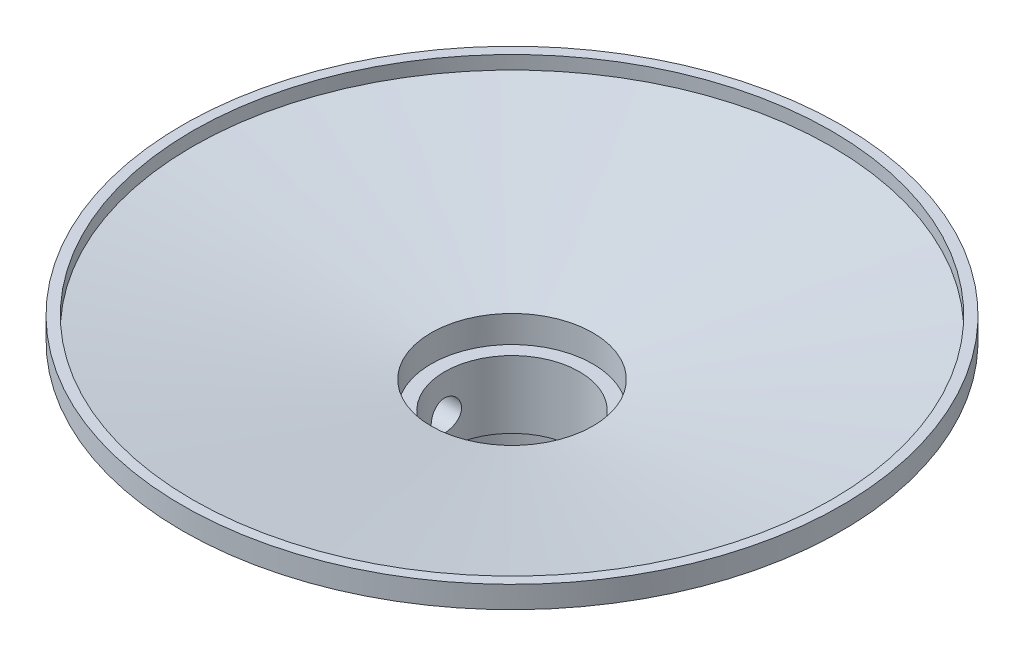
SolidWorks part; units mm, degrees
ref_plane "Front Plane" through (0, 0, 0) normal (0, 0, 1) x (1, 0, 0)
ref_plane "Top Plane" through (0, 0, 0) normal (0, 1, 0) x (1, 0, 0)
ref_plane "Right Plane" through (0, 0, 0) normal (1, 0, 0) x (0, 0, -1)
sketch "Sketch5" plane through (0, 0, 0) normal (1, 0, 0) x (0, 0, -1)
  line L0 (0, 0) -> (0, 10.2777) construction
  line L1 (0, 0) -> (48.9, 0) construction
  line L2 (48.9, 0) -> (48.9, -3.2586)
  line L3 (48.9, -3.2586) -> (13.5, -9.5006)
  line L4 (13.5, -9.5006) -> (13.5, -22.242)
  line L5 (10, -22.242) -> (12, -22.242)
  line L6 (47.4, 0) -> (47.4, -2)
  line L7 (47.4, -2) -> (12, -8.242)
  line L8 (12, -8.242) -> (12, -12.242)
  line L9 (12, -22.242) -> (12, -26.242)
  line L10 (12, -12.242) -> (10, -12.242)
  line L11 (10, -12.242) -> (10, -22.242)
  line L12 (12, -8.242) -> (12, -21.6264) construction
  line L13 (12, -21.6264) -> (0.1924, -33.5895) construction
  line L14 (13.5, -22.242) -> (1.26, -34.6432) construction
  line L15 (12, -26.242) -> (13.5, -26.242)
  line L16 (13.5, -26.242) -> (13.5, -22.242)
  line L17 (47.4, -2) -> (0, -2) construction
  line L18 (47.4, 0) -> (48.9, 0)
  dimension "D1" = 48.9
  dimension "D3" = 10
  dimension "D4" = 2
  dimension "D5" = 4
  dimension "D6" = 10
  dimension "D7" = 2
  dimension "D8" = 10
  dimension "D2" = 1.5
revolve "Revolve5" add sketch "Sketch5" angle 360 about L0 region at (0, -1.6293, -48.4308)
sketch "Sketch6" plane through (0, 0, 0) normal (1, 0, 0) x (0, 0, -1)
  line L0 (-13.5, -9.5006) -> (-13.5, -26.242) construction
  line L1 (-13.5, -9.5006) -> (-13.5, -26.242)
  line L2 (-13.5, -17.8713) -> (0, -17.8713)
  circle A0 centre (0, -17.8713) radius 2.25
  point P5 (-13.5, -17.8713)
  point P7 (0, -21.242)
  point P8 (0, 0)
  dimension "D1" = 4.5
extrude "Cut-Extrude6" cut sketch "Sketch6" against normal through all contours A0 region at (0, -20.0577, 0)
equation "\"D1@Sketch5\"=97.8/2"
